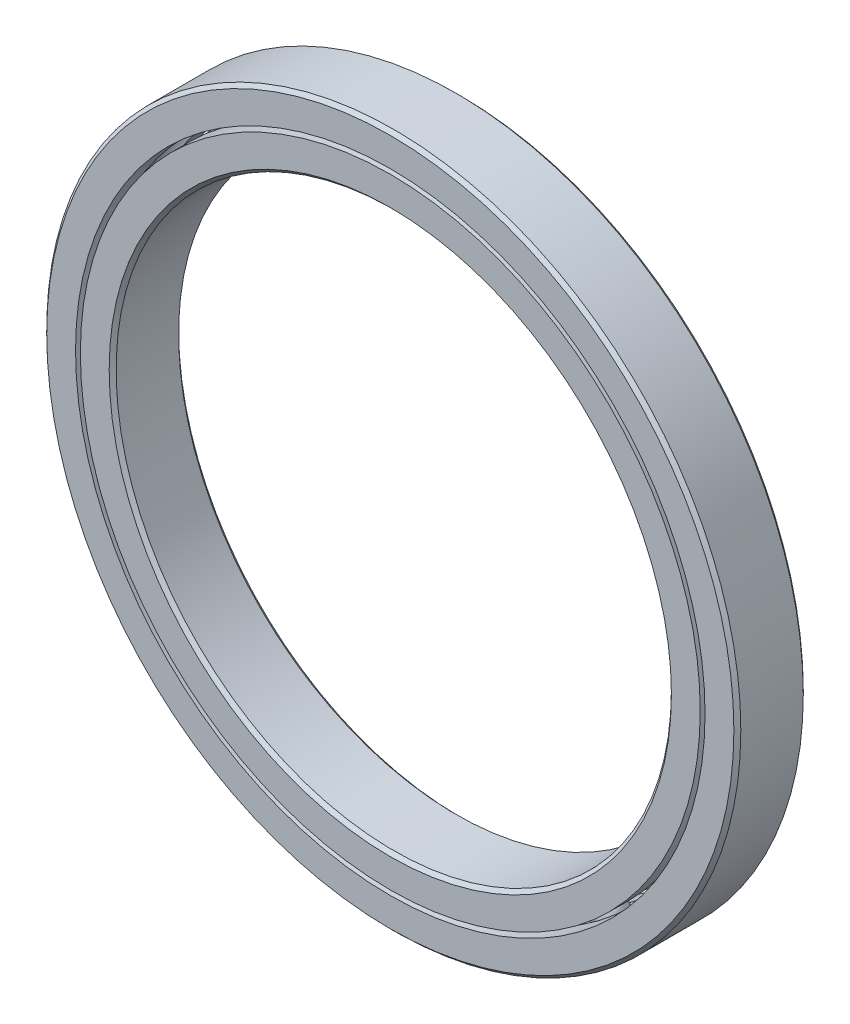
SolidWorks part; units mm, degrees
ref_plane "Front Plane" through (0, 0, 0) normal (0, 0, 1) x (1, 0, 0)
ref_plane "Top Plane" through (0, 0, 0) normal (0, 1, 0) x (1, 0, 0)
ref_plane "Right Plane" through (0, 0, 0) normal (1, 0, 0) x (0, 0, -1)
sketch "Sketch1" plane through (0, 0, 0) normal (1, 0, 0) x (0, 0, -1)
  line L0 (-3.175, 0) -> (3.175, 0) construction
  line L1 (0, 31.75) -> (0, -31.75) construction
  line L2 (2.8575, 31.75) -> (-2.8575, 31.75)
  line L3 (-2.8575, 31.75) -> (-3.175, 31.4325)
  line L4 (-3.175, 31.4325) -> (-3.175, 28.7948)
  line L5 (-3.175, 28.7948) -> (-1.4111, 28.7948)
  line L6 (3.175, 28.7948) -> (1.4111, 28.7948)
  line L7 (3.175, 31.4325) -> (3.175, 28.7948)
  line L8 (2.8575, 31.75) -> (3.175, 31.4325)
  line L9 (0, 31.75) -> (0, 28.575) construction
  line L10 (0, 28.575) -> (0, 25.4) construction
  arc A0 (-1.4111, 28.7948) -> (1.4111, 28.7948) centre (0, 28.575) cw
  point P14 (0, 25.4)
  dimension "D3" = 2.8222
  dimension "D1" = 45
  dimension "Width" = 6.35
  dimension "OD" = 63.5
  dimension "D2" = 0.3175
  dimension "Shaft Dia" = 50.8
  dimension "D4" = 0.2198
revolve "Revolve1" add sketch "Sketch1" angle 360 about L0
sketch "Sketch3" plane through (0, 0, 0) normal (1, 0, 0) x (0, 0, -1)
  line L0 (-3.175, 28.3552) -> (-1.4111, 28.3552)
  line L1 (0, 31.75) -> (0, -31.75) construction
  line L2 (-3.175, 31.4325) -> (-3.175, 28.7948) construction
  line L3 (-3.175, 28.3552) -> (-3.175, 25.7175)
  line L4 (-2.8575, 31.75) -> (-3.175, 31.4325) construction
  line L5 (-3.175, 25.7175) -> (-2.8575, 25.4)
  line L6 (-2.8575, 25.4) -> (2.8575, 25.4)
  line L7 (2.8575, 31.75) -> (2.8575, -31.75) construction
  line L8 (2.8575, 25.4) -> (3.175, 25.7175)
  line L9 (3.175, -31.4325) -> (3.175, 31.4325) construction
  line L10 (3.175, 25.7175) -> (3.175, 28.3552)
  line L11 (3.175, 28.3552) -> (1.4111, 28.3552)
  line L13 (2.8575, 31.75) -> (3.175, 31.4325) construction
  arc A0 (1.4111, 28.7948) -> (-1.4111, 28.7948) centre (0, 28.575) ccw construction
  arc A1 (1.4111, 28.3552) -> (-1.4111, 28.3552) centre (0, 28.575) cw
revolve "Revolve3" add sketch "Sketch3" angle 360 about L0
sketch "Sketch4" plane through (0, 0, 0) normal (1, 0, 0) x (0, 0, -1)
  line L0 (-1.4281, 28.575) -> (1.4281, 28.575)
  arc A2 (-1.4281, 28.575) -> (1.4281, 28.575) centre (0, 28.575) cw
  arc A3 (1.4111, 28.7948) -> (-1.4111, 28.7948) centre (0, 28.575) ccw construction
revolve "Revolve4" add sketch "Sketch4" angle 360 about L0
ref_axis "Axis1" through (0, 0, -3.175) along (0, 0, 1)
pattern_circular "CirPattern1" count 10 every 36 about axis through (0, 0, -3.175) along (0, 0, 1) of bodies 104
equation "\"D2@Sketch1\" = \"Width@Sketch1\"*.05"
equation "\"D3@Sketch1\" = \"Width@Sketch1\"/2.25"
equation "\"D4@Sketch1\" = (((\"OD@Sketch1\"-\"Width@Sketch1\")/2)/3.25)*.025"
equation "\"D2@CirPattern1\" = 360/\"Balls@CirPattern1\""
